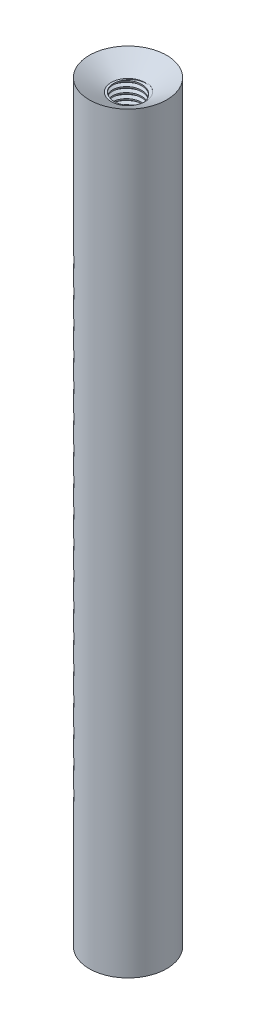
SolidWorks part; units mm, degrees
material "A286 Iron Base Superalloy"
ref_plane "Front Plane" through (0, 0, 0) normal (0, 0, 1) x (1, 0, 0)
ref_plane "Top Plane" through (0, 0, 0) normal (0, 1, 0) x (1, 0, 0)
ref_plane "Right Plane" through (0, 0, 0) normal (1, 0, 0) x (0, 0, -1)
sketch "Sketch1" plane through (0, 0, 0) normal (0, 1, 0) x (1, 0, 0)
  circle A0 centre (0, 0) radius 9.25
  dimension "D1" = 18.5
extrude "Boss-Extrude1" add sketch "Sketch1" along normal blind 180 contours A0
sketch "Sketch6" plane through (0, 0, 0) normal (0, 0, 1) x (1, 0, 0)
  line L0 (0, 270.9695) -> (0, -68.2304) construction
  line L1 (77.6113, 90) -> (-130.0621, 90) construction
  line L2 (9.25, 180) -> (-9.25, 180) construction
  line L4 (0, 177) -> (4, 177)
  line L5 (4, 177) -> (39.3146, 197.1798)
  line L6 (39.3146, 197.1798) -> (0, 197.1798)
  line L7 (0, 197.1798) -> (0, 177)
  line L8 (0, 3) -> (4, 3)
  line L9 (0, -17.1798) -> (0, 3)
  line L10 (39.3146, -17.1798) -> (0, -17.1798)
  line L11 (4, 3) -> (39.3146, -17.1798)
  dimension "D1" = 90
  dimension "D2" = 3
  dimension "D3" = 4
  dimension "D4" = 20.1798
revolve "Cut-Revolve2" cut sketch "Sketch6" angle 360 about L0
hole_wizard "M8x1.0 Tapped Hole1" positions "Sketch11" profile "Sketch12" tap size "M8x1.0" standard "ISO"
sketch "Sketch11" plane through (0, 177, 0) normal (0, 1, 0) x (1, 0, 0)
  point P0 (0, 0)
sketch "Sketch12" plane through (0, 177, 0) normal (1, 0, 0) x (0, 0, 1)
  line L0 (0, 0) -> (0, 19)
  line L1 (0, 19) -> (3.5, 16.897)
  line L2 (3.5, 16.897) -> (3.5, 0)
  line L5 (3.5, 0) -> (0, 0)
  line L10 (0, 19) -> (-3.5, 16.897) construction
  line L11 (0, -6.35) -> (0, 107.95) construction
  dimension "Tap Drill Dia." = 7
  dimension "Tap Drill Depth" = 19
  dimension "Drill Angle" = 118
cosmetic thread "Hole Thread1" parameters "D1"=16, "D2"=8
hole_wizard "M8x1.0 Tapped Hole2" positions "Sketch14" profile "Sketch15" tap size "M8x1.0" standard "ISO"
sketch "Sketch14" plane through (0, 3, 0) normal (0, -1, 0) x (-1, 0, 0)
  point P0 (0, 0)
sketch "Sketch15" plane through (0, 3, 0) normal (1, 0, 0) x (0, 0, -1)
  line L0 (0, 0) -> (0, 19)
  line L1 (0, 19) -> (3.5, 16.897)
  line L2 (3.5, 16.897) -> (3.5, 0)
  line L5 (3.5, 0) -> (0, 0)
  line L10 (0, 19) -> (-3.5, 16.897) construction
  line L11 (0, -6.35) -> (0, 107.95) construction
  dimension "Tap Drill Dia." = 7
  dimension "Tap Drill Depth" = 19
  dimension "Drill Angle" = 118
cosmetic thread "Hole Thread2" parameters "D1"=16, "D2"=8
sketch "Sketch16" plane through (0, 0, 0) normal (0, 0, 1) x (1, 0, 0)
  line L0 (-9.25, 34.5) -> (-9.25, 29.5)
  line L1 (-9.25, 180) -> (-9.25, 0) construction
  line L3 (-5.25, 33.1) -> (-5.25, 30.9)
  line L5 (-21.6928, 32) -> (13.6331, 32) construction
  line L7 (-5.25, 33.1) -> (-9.25, 34.5)
  line L8 (-5.25, 30.9) -> (-9.25, 29.5)
  line L10 (-9.25, 41) -> (-9.25, 36)
  line L11 (-5.25, 39.6) -> (-9.25, 41)
  line L12 (-5.25, 39.6) -> (-5.25, 37.4)
  line L13 (-5.25, 37.4) -> (-9.25, 36)
  line L14 (-9.25, 47.5) -> (-9.25, 42.5)
  line L15 (-5.25, 46.1) -> (-9.25, 47.5)
  line L16 (-5.25, 46.1) -> (-5.25, 43.9)
  line L17 (-5.25, 43.9) -> (-9.25, 42.5)
  line L18 (-9.25, 54) -> (-9.25, 49)
  line L19 (-5.25, 52.6) -> (-9.25, 54)
  line L20 (-5.25, 52.6) -> (-5.25, 50.4)
  line L21 (-5.25, 50.4) -> (-9.25, 49)
  line L22 (-9.25, 60.5) -> (-9.25, 55.5)
  line L23 (-5.25, 59.1) -> (-9.25, 60.5)
  line L24 (-5.25, 59.1) -> (-5.25, 56.9)
  line L25 (-5.25, 56.9) -> (-9.25, 55.5)
  line L26 (-9.25, 67) -> (-9.25, 62)
  line L27 (-5.25, 65.6) -> (-9.25, 67)
  line L28 (-5.25, 65.6) -> (-5.25, 63.4)
  line L29 (-5.25, 63.4) -> (-9.25, 62)
  line L30 (-9.25, 73.5) -> (-9.25, 68.5)
  line L31 (-5.25, 72.1) -> (-9.25, 73.5)
  line L32 (-5.25, 72.1) -> (-5.25, 69.9)
  line L33 (-5.25, 69.9) -> (-9.25, 68.5)
  line L34 (-9.25, 80) -> (-9.25, 75)
  line L35 (-5.25, 78.6) -> (-9.25, 80)
  line L36 (-5.25, 78.6) -> (-5.25, 76.4)
  line L37 (-5.25, 76.4) -> (-9.25, 75)
  line L38 (-9.25, 86.5) -> (-9.25, 81.5)
  line L39 (-5.25, 85.1) -> (-9.25, 86.5)
  line L40 (-5.25, 85.1) -> (-5.25, 82.9)
  line L41 (-5.25, 82.9) -> (-9.25, 81.5)
  line L42 (-9.25, 93) -> (-9.25, 88)
  line L43 (-5.25, 91.6) -> (-9.25, 93)
  line L44 (-5.25, 91.6) -> (-5.25, 89.4)
  line L45 (-5.25, 89.4) -> (-9.25, 88)
  line L46 (-9.25, 99.5) -> (-9.25, 94.5)
  line L47 (-5.25, 98.1) -> (-9.25, 99.5)
  line L48 (-5.25, 98.1) -> (-5.25, 95.9)
  line L49 (-5.25, 95.9) -> (-9.25, 94.5)
  line L50 (-9.25, 106) -> (-9.25, 101)
  line L51 (-5.25, 104.6) -> (-9.25, 106)
  line L52 (-5.25, 104.6) -> (-5.25, 102.4)
  line L53 (-5.25, 102.4) -> (-9.25, 101)
  line L54 (-9.25, 112.5) -> (-9.25, 107.5)
  line L55 (-5.25, 111.1) -> (-9.25, 112.5)
  line L56 (-5.25, 111.1) -> (-5.25, 108.9)
  line L57 (-5.25, 108.9) -> (-9.25, 107.5)
  line L58 (-9.25, 119) -> (-9.25, 114)
  line L59 (-5.25, 117.6) -> (-9.25, 119)
  line L60 (-5.25, 117.6) -> (-5.25, 115.4)
  line L61 (-5.25, 115.4) -> (-9.25, 114)
  line L62 (-9.25, 125.5) -> (-9.25, 120.5)
  line L63 (-5.25, 124.1) -> (-9.25, 125.5)
  line L64 (-5.25, 124.1) -> (-5.25, 121.9)
  line L65 (-5.25, 121.9) -> (-9.25, 120.5)
  line L66 (-9.25, 132) -> (-9.25, 127)
  line L67 (-5.25, 130.6) -> (-9.25, 132)
  line L68 (-5.25, 130.6) -> (-5.25, 128.4)
  line L69 (-5.25, 128.4) -> (-9.25, 127)
  line L70 (-9.25, 138.5) -> (-9.25, 133.5)
  line L71 (-5.25, 137.1) -> (-9.25, 138.5)
  line L72 (-5.25, 137.1) -> (-5.25, 134.9)
  line L73 (-5.25, 134.9) -> (-9.25, 133.5)
  line L74 (-9.25, 145) -> (-9.25, 140)
  line L75 (-5.25, 143.6) -> (-9.25, 145)
  line L76 (-5.25, 143.6) -> (-5.25, 141.4)
  line L77 (-5.25, 141.4) -> (-9.25, 140)
  line L78 (-9.25, 180) -> (9.25, 180) construction
  point P0 (-5.25, 32)
  point P11 (-9.25, 32)
  dimension "D1" = 5
  dimension "D2" = 2.2
  dimension "D3" = 4
  dimension "D4" = 35
  dimension "D6" = 1.5
  dimension "D5" = 18
extrude "Cut-Extrude2" cut sketch "Sketch16" against normal through all both and the other way through all
thread "Thread1" pitch 1.25 method cut profile "Thread Profile1" start angle 0, offset 1, length 15, pitch 1.25, diameter 7
ref_plane "Plane1" through (3.5, 2, 0) normal (0, 0, 1) x (1, 0, 0)
sketch "Thread Profile1" plane through (3.5, 2, 0) normal (0, 0, 1) x (1, 0, 0)
  line L0 (0, 0) -> (0, 1.25) construction
  line L1 (0, 0) -> (0.6766, 0.3906)
  line L2 (0.6766, 0.3906) -> (0.6766, 0.5469)
  line L3 (0.6766, 0.5469) -> (0, 0.9375)
  line L4 (0.6766, 0.4687) -> (0, 0.4687) construction
  line L11 (0, 0) -> (0, 0.9375)
  point P2 (0, 0)
  dimension "Pitch" = 1.25
  dimension "Profile_Angle" = 60
  dimension "Profile_Land" = 0.1562
  dimension "Profile_Height" = 0.6766
thread "Thread2" pitch 1.25 method cut profile "Thread Profile3" start angle 0, offset 1, length 15, pitch 1.25, diameter 7
ref_plane "Plane3" through (-3.5, 178, 0) normal (0, 0, 1) x (-1, 0, 0)
sketch "Thread Profile3" plane through (-3.5, 178, 0) normal (0, 0, 1) x (-1, 0, 0)
  line L0 (0, 0) -> (0, 1.25) construction
  line L1 (0, 0) -> (0.6766, 0.3906)
  line L2 (0.6766, 0.3906) -> (0.6766, 0.5469)
  line L3 (0.6766, 0.5469) -> (0, 0.9375)
  line L4 (0.6766, 0.4687) -> (0, 0.4687) construction
  line L11 (0, 0) -> (0, 0.9375)
  point P2 (0, 0)
  dimension "Pitch" = 1.25
  dimension "Profile_Angle" = 60
  dimension "Profile_Land" = 0.1562
  dimension "Profile_Height" = 0.6766
